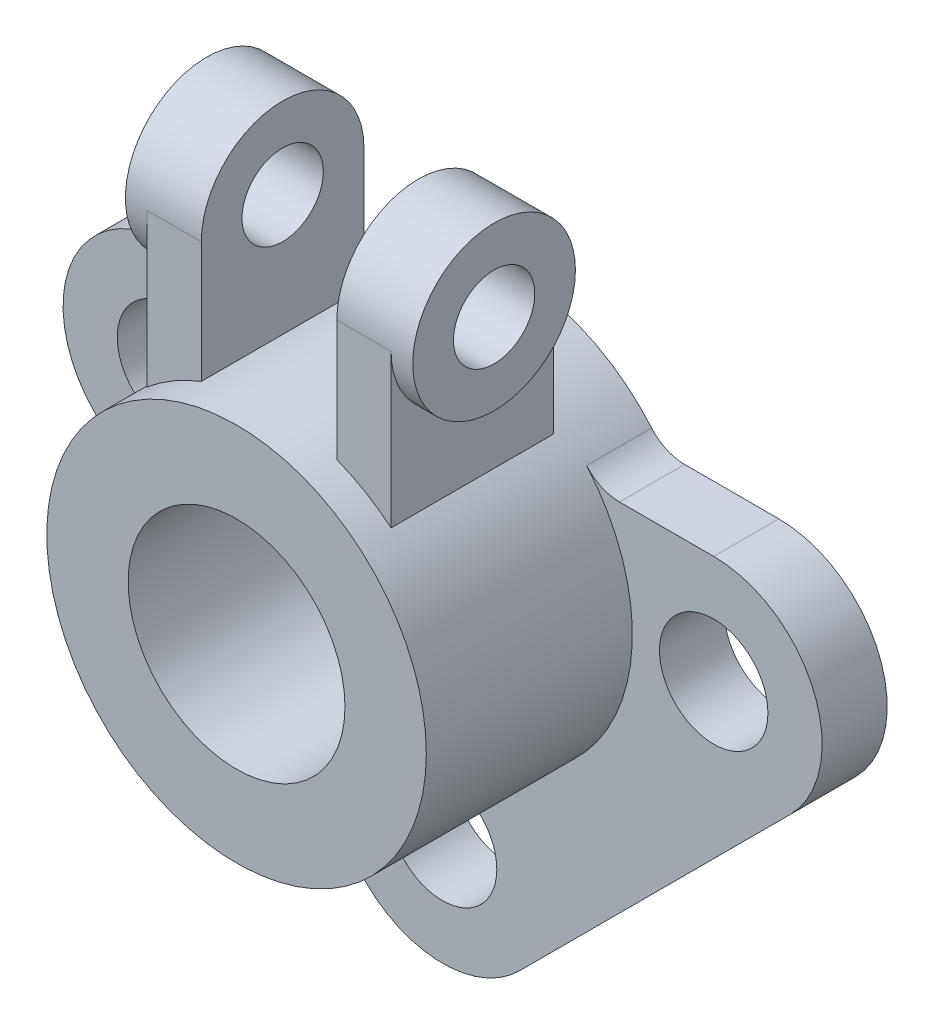
SolidWorks part; units mm, degrees
ref_plane "Front Plane" through (0, 0, 0) normal (0, 0, 1) x (1, 0, 0)
ref_plane "Top Plane" through (0, 0, 0) normal (0, 1, 0) x (1, 0, 0)
ref_plane "Right Plane" through (0, 0, 0) normal (1, 0, 0) x (0, 0, -1)
sketch "Sketch1" plane through (0, 0, 0) normal (0, 0, 1) x (1, 0, 0)
  line L0 (0, 51.2663) -> (0, -78.2843) construction
  line L1 (14.1421, -64.1421) -> (64.1421, -14.1421)
  line L2 (50, 20) -> (28.7228, 20)
  line L3 (-64.1421, -14.1421) -> (-14.1421, -64.1421)
  line L4 (-28.7228, 20) -> (-50, 20)
  circle A0 centre (0, 0) radius 35
  circle A1 centre (0, 0) radius 20
  arc A2 (64.1421, -14.1421) -> (50, 20) centre (50, 0) ccw
  arc A3 (-50, 20) -> (-64.1421, -14.1421) centre (-50, 0) ccw
  arc A4 (14.1421, -64.1421) -> (-14.1421, -64.1421) centre (0, -50) cw
  circle A5 centre (50, 0) radius 10
  circle A6 centre (-50, 0) radius 10
  circle A7 centre (0, -50) radius 10
  point P18 (0, -47.3592)
  point P19 (0, -47.3595)
  point P20 (0, -31.9611)
  point P21 (0, -37.7343)
  dimension "D1" = 40
  dimension "D2" = 50
  dimension "D3" = 20
  dimension "D4" = 20
  dimension "D5" = 100
  dimension "D6" = 50
extrude "Boss-Extrude1" add sketch "Sketch1" along normal blind 12 contours A0 L0 A7 A4 L1 A2 L2 A5 | L0 A0 L4 A3 L3 A4 A7 A6 region at (35.692, -21.9559, 0) region at (-35.692, -21.9559, 0)
extrude "Boss-Extrude2" add sketch "Sketch1<3>" along normal blind 50 contours L0 A0 A1 | A0 L0 A1 region at (15.8396, 30.3305, 0) region at (-0.7826, 27.5, 0)
sketch "Sketch1<3>" plane through (0, 0, 0) normal (0, 0, 1) x (1, 0, 0) same geometry as "Sketch1"
fillet "Fillet1" radius 8 2 edges at (-28.7228, 20, 6) (28.7228, 20, 6)
sketch "Sketch2" plane through (0, 0, 50) normal (0, 0, 1) x (1, 0, 0)
  line L0 (0, 0) -> (0, 85.0216) construction
  line L1 (12.5, 32.6917) -> (12.5, 70)
  line L2 (12.5, 70) -> (22.5, 70)
  line L3 (22.5, 70) -> (22.5, 26.8095)
  line L4 (-22.5, 70) -> (-22.5, 26.8095)
  line L5 (-12.5, 70) -> (-22.5, 70)
  line L6 (-12.5, 32.6917) -> (-12.5, 70)
  circle A0 centre (0, 0) radius 35 construction
  arc A1 (22.5, 26.8095) -> (0, 35) centre (0, 0) ccw
  circle M7 centre (0, 0) radius 35
  dimension "D1" = 70
  dimension "D2" = 10
  dimension "D3" = 25
extrude "Boss-Extrude3" add sketch "Sketch2" against normal blind 30 from offset 6 contours L6 L5 L4 M7 | L3 L2 L1 M7 region at (17.622, 50.0268, 50) region at (-17.622, 50.0268, 50) offset against normal yes
sketch "Sketch3" plane through (22.5, 0, 0) normal (1, 0, 0) x (0, 0, -1)
  line L0 (-14, 70) -> (-44, 70) construction
  line L1 (-14, 70) -> (-14, 26.8095) construction
  circle A0 centre (-29, 55) radius 15
  circle A1 centre (-29, 55) radius 7.5
  line M1 (-44, 70) -> (-44, 26.8095)
  line M3 (-14, 26.8095) -> (-14, 70)
  line M4 (-14, 70) -> (-44, 70)
  dimension "D1" = 15
  dimension "D2" = 30
extrude "Cut-Extrude1" cut sketch "Sketch3" against normal through all contours A1 | A0 M4 M1 | A0 M3 M4 region at (22.5, 66.6495, 17.3505) region at (22.5, 66.6495, 40.6495) region at (22.5, 55, 29)
extrude "Boss-Extrude4" add sketch "Sketch3<3>" along normal blind 4
sketch "Sketch3<3>" plane through (22.5, 0, 0) normal (1, 0, 0) x (0, 0, -1) same geometry as "Sketch3"
mirror "Mirror1" about plane through (0, 0, 0) normal (1, 0, 0) of "Boss-Extrude4"
